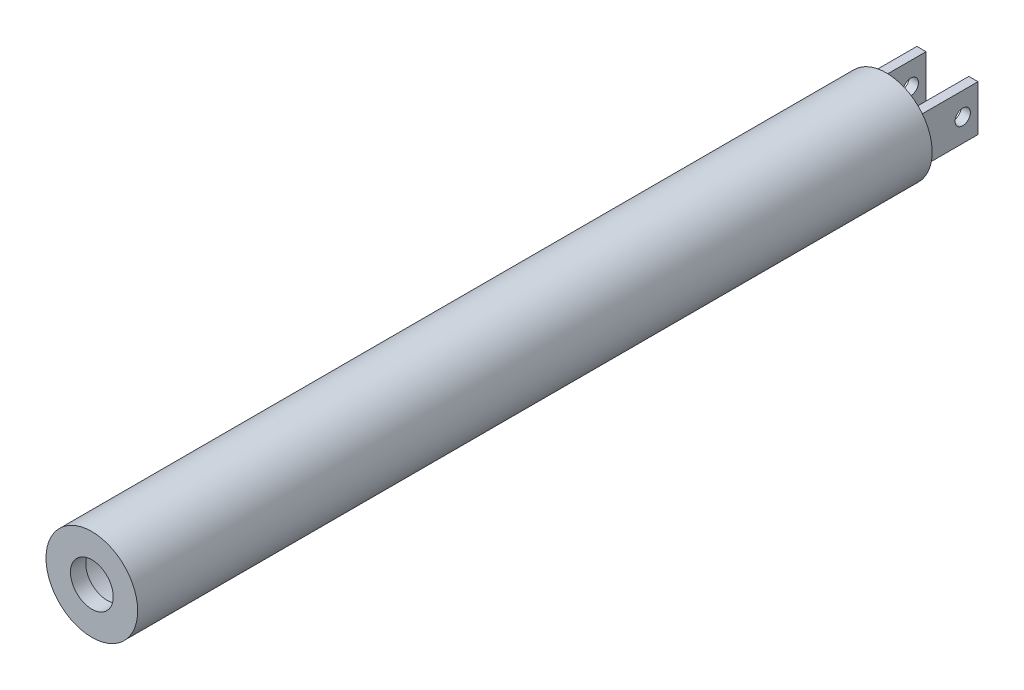
SolidWorks part; units mm, degrees
ref_plane "Front Plane" through (0, 0, 0) normal (0, 0, 1) x (1, 0, 0)
ref_plane "Top Plane" through (0, 0, 0) normal (0, 1, 0) x (1, 0, 0)
ref_plane "Right Plane" through (0, 0, 0) normal (1, 0, 0) x (0, 0, -1)
sketch "Sketch1" plane through (0, 0, 0) normal (0, 0, 1) x (1, 0, 0)
  circle A0 centre (0, 0) radius 15
  circle A1 centre (0, 0) radius 13.5
  dimension "D1" = 30
  dimension "D2" = 27
extrude "Boss-Extrude1" add sketch "Sketch1" along normal blind 250
sketch "Sketch2" plane through (0, 0, 0) normal (0, 0, -1) x (-1, 0, 0)
  circle A0 centre (0, 0) radius 15
extrude "Boss-Extrude2" add sketch "Sketch2" along normal blind 5
sketch "Sketch3" plane through (0, 0, 250) normal (0, 0, 1) x (1, 0, 0)
  circle A0 centre (0, 0) radius 15
  circle A1 centre (0, 0) radius 7
  dimension "D1" = 14
extrude "Boss-Extrude3" add sketch "Sketch3" along normal blind 5
sketch "Sketch4" plane through (0, 0, 0) normal (1, 0, 0) x (0, 0, -1)
  line L0 (25, -7.5) -> (5, -7.5)
  line L1 (25, -7.5) -> (25, 7.5)
  line L2 (5, -7.5) -> (5, 7.5)
  line L3 (25, 7.5) -> (5, 7.5)
  line L4 (5, 0) -> (25, 0) construction
  line L5 (15, -7.5) -> (15, 7.5) construction
  line L6 (5, -15) -> (5, 15) construction
  circle A0 centre (20, 0) radius 2.5
  point P1 (15, 0)
  dimension "D3" = 5
  dimension "D4" = 5
  dimension "D1" = 15
  dimension "D2" = 20
extrude "Boss-Extrude4" add sketch "Sketch4" along normal blind 10 and the other way blind 10
sketch "Sketch5" plane through (0, 0, -25) normal (0, 0, -1) x (-1, 0, 0)
  line L0 (10, 7.5) -> (-10, 7.5) construction
  line L1 (-7, -7.5) -> (7, -7.5)
  line L2 (-7, -7.5) -> (-7, 7.5)
  line L3 (-7, 7.5) -> (7, 7.5)
  line L4 (7, -7.5) -> (7, 7.5)
  line L5 (0, 7.5) -> (0, -7.5) construction
  line L6 (-7, 0) -> (7, 0) construction
  line L7 (-10, 7.5) -> (-10, -7.5) construction
  point P0 (0, 0)
  dimension "D1" = 3
extrude "Cut-Extrude1" cut sketch "Sketch5" against normal up to surface (20 mm away) up to face at (-15, 0, -5)
